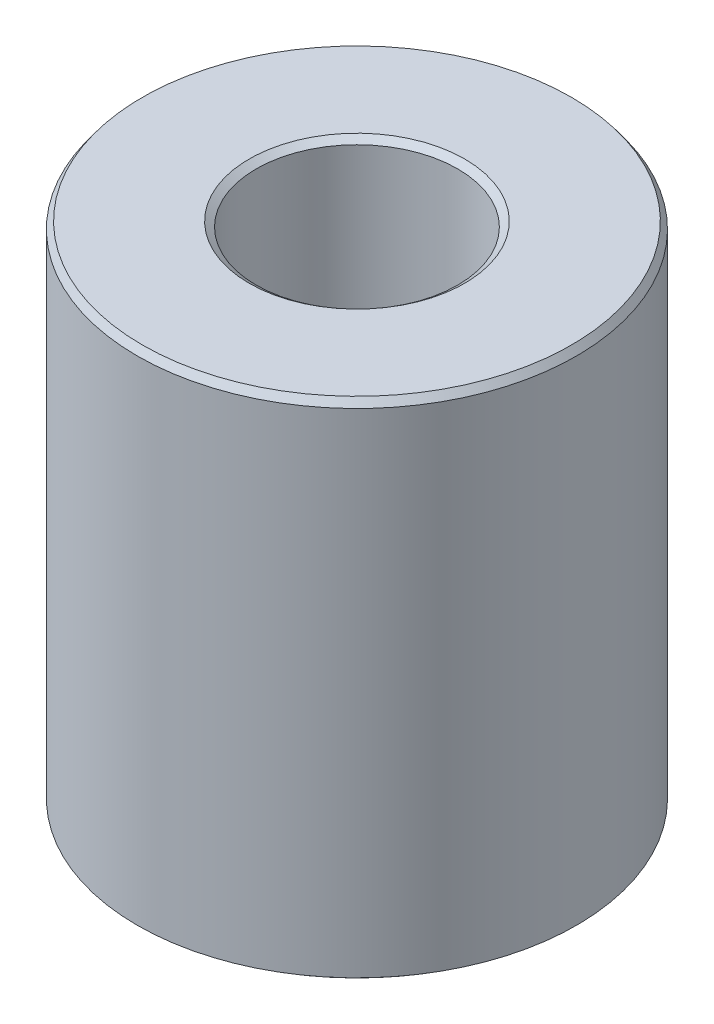
SolidWorks part; units mm, degrees
ref_plane "Front Plane" through (0, 0, 0) normal (0, 0, 1) x (1, 0, 0)
ref_plane "Top Plane" through (0, 0, 0) normal (0, 1, 0) x (1, 0, 0)
ref_plane "Right Plane" through (0, 0, 0) normal (1, 0, 0) x (0, 0, -1)
sketch "Sketch1" plane through (0, 0, 0) normal (0, 1, 0) x (1, 0, 0)
  circle A0 centre (0, 0) radius 55
  dimension "SLEEVE_OD" = 110
extrude "Boss-Extrude1" add sketch "Sketch1" along normal blind 126.514
sketch "Sketch2" plane through (0, 0, 0) normal (0, 1, 0) x (1, 0, 0)
  circle A0 centre (0, 0) radius 25.2301
  dimension "BORE_D" = 50.4601
extrude "Cut-Extrude1" cut sketch "Sketch2" along normal through all
chamfer "Chamfer1" distance 1.7529 angle 35.82 4 edges at (0, 126.514, 25.2301) (0, 0, 25.2301) (0, 0, 55) (0, 126.514, 55) first distance on face at (0, 126.514, 25.2301) first distance on face at (0, 0, 25.2301) first distance on face at (0, 126.514, 55)
